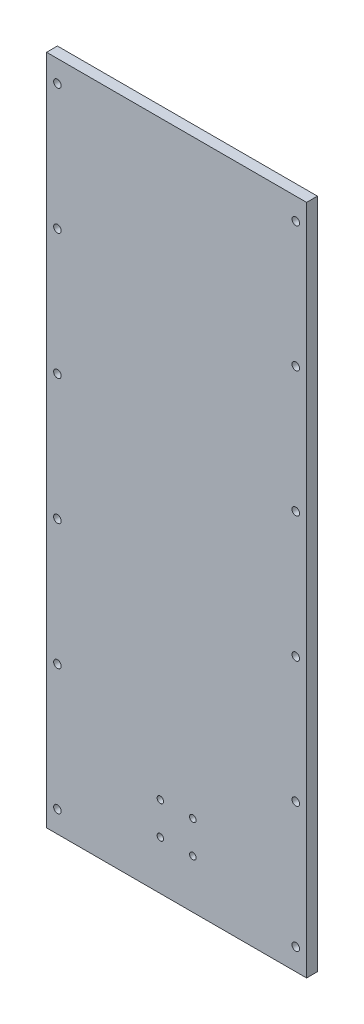
SolidWorks part; units mm, degrees
ref_plane "Plan de face" through (0, 0, 0) normal (0, 0, 1) x (1, 0, 0)
ref_plane "Plan de dessus" through (0, 0, 0) normal (0, 1, 0) x (1, 0, 0)
ref_plane "Plan de droite" through (0, 0, 0) normal (1, 0, 0) x (0, 0, -1)
sketch "Esquisse1" plane through (0, 0, 0) normal (0, 0, 1) x (1, 0, 0)
  line L1 (60, -155) -> (-60, -155)
  line L2 (60, -155) -> (60, 155)
  line L3 (60, 155) -> (-60, 155)
  line L4 (-60, -155) -> (-60, 155)
  line L5 (60, -155) -> (-60, 155) construction
  line L6 (60, 155) -> (-60, -155) construction
  point P0 (0, 0)
  dimension "D1" = 310
  dimension "D2" = 120
extrude "Boss.-Extru.1" add sketch "Esquisse1" along normal blind 5
sketch "Esquisse2" plane through (0, 0, 5) normal (0, 0, 1) x (1, 0, 0)
  line L0 (60, 155) -> (-60, 155) construction
  line L2 (-55, 145) -> (60, 145) construction
  line L3 (60, -155) -> (60, 155) construction
  line L4 (-55, 145) -> (-55, -155) construction
  line L5 (-60, -155) -> (60, -155) construction
  line L6 (-7.5, -117.5) -> (7.5, -117.5) construction
  line L7 (0, 0) -> (0, -155) construction
  line L8 (7.5, -137.5) -> (-7.5, -137.5) construction
  line L9 (12.5, -132.5) -> (12.5, -117.5) construction
  line L10 (7.5, -112.5) -> (-7.5, -112.5) construction
  line L11 (-12.5, -132.5) -> (-12.5, -117.5) construction
  line L12 (12.5, -137.5) -> (-12.5, -112.5) construction
  line L13 (12.5, -112.5) -> (-12.5, -137.5) construction
  line L14 (-7.5, -117.5) -> (-7.5, -132.5) construction
  line L15 (55, 145) -> (55, -155) construction
  circle A0 centre (-55, 145) radius 1.7476
  circle A2 centre (55, 145) radius 1.7476
  circle A3 centre (-55, 87) radius 1.7476
  circle A4 centre (-55, 29) radius 1.7476
  circle A5 centre (-55, -29) radius 1.7476
  circle A6 centre (-55, -87) radius 1.7476
  circle A11 centre (55, 87) radius 1.7476
  circle A12 centre (55, 29) radius 1.7476
  circle A13 centre (55, -29) radius 1.7476
  circle A14 centre (55, -87) radius 1.7476
  circle A15 centre (0, -125) radius 4.5 construction
  arc A16 (7.5, -137.5) -> (12.5, -132.5) centre (7.5, -132.5) ccw construction
  arc A17 (-7.5, -137.5) -> (-12.5, -132.5) centre (-7.5, -132.5) cw construction
  arc A18 (12.5, -117.5) -> (7.5, -112.5) centre (7.5, -117.5) ccw construction
  arc A19 (-7.5, -112.5) -> (-12.5, -117.5) centre (-7.5, -117.5) ccw construction
  circle A20 centre (-7.5, -117.5) radius 1.5
  circle A21 centre (7.5, -117.5) radius 1.5
  circle A22 centre (7.5, -132.5) radius 1.5
  circle A23 centre (-7.5, -132.5) radius 1.5
  circle A24 centre (55, -145) radius 1.7476
  circle A25 centre (0, 145) radius 1.7476 [skipped]
  circle A26 centre (-55, -145) radius 1.7476
  point P4 (0, 0)
  dimension "D8" = 9
  dimension "D10" = 5
  dimension "D12" = 3
  dimension "D1" = 10
  dimension "D2" = 10
  dimension "D4" = 5
  dimension "D6" = 10
  dimension "D9" = 30
  dimension "D11" = 25
  dimension "D3" = 3
  dimension "D5" = 6
  dimension "D13" = 2
  dimension "D14" = 2
extrude "Enlèv. mat.-Extru.1" cut sketch "Esquisse2" against normal blind 10
